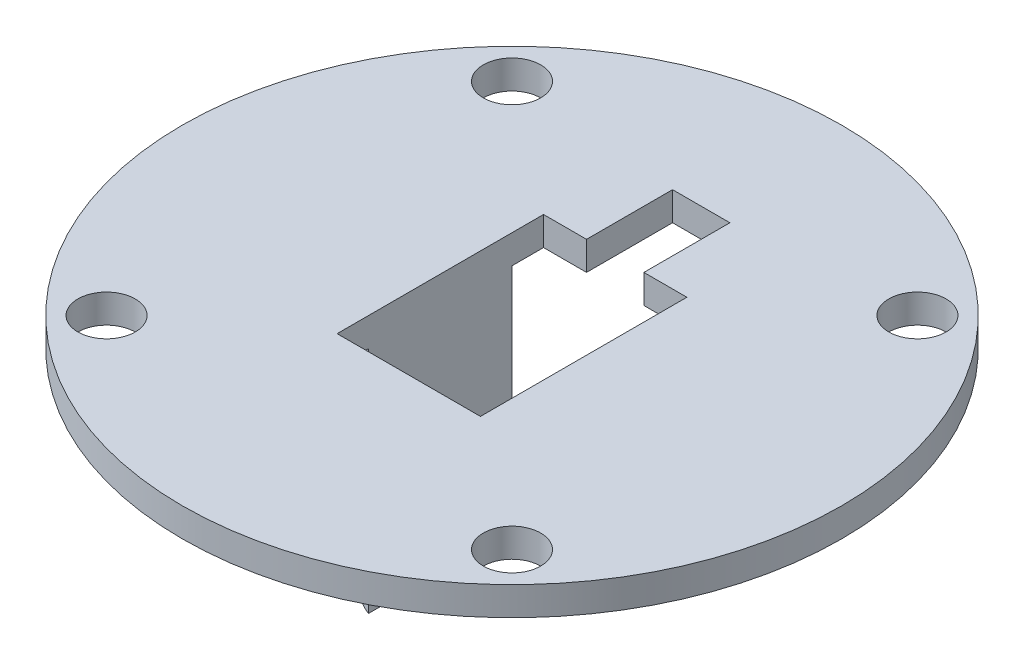
SolidWorks part; units mm, degrees
ref_plane "Front Plane" through (0, 0, 0) normal (0, 0, 1) x (1, 0, 0)
ref_plane "Top Plane" through (0, 0, 0) normal (0, 1, 0) x (1, 0, 0)
ref_plane "Right Plane" through (0, 0, 0) normal (1, 0, 0) x (0, 0, -1)
sketch "Sketch2" plane through (0, 0, 0) normal (0, 1, 0) x (1, 0, 0)
  circle A0 centre (0, 0) radius 57.5
  dimension "D1" = 115
extrude "Boss-Extrude1" add sketch "Sketch2" along normal blind 5
sketch "Sketch3" plane through (0, 5, 0) normal (0, 1, 0) x (1, 0, 0)
  line L0 (-35.3553, -35.3553) -> (35.3553, -35.3553) construction
  line L1 (35.3553, -35.3553) -> (35.3553, 35.3553) construction
  line L2 (35.3553, 35.3553) -> (-35.3553, 35.3553) construction
  line L3 (-35.3553, 35.3553) -> (-35.3553, -35.3553) construction
  circle A0 centre (-35.3553, 35.3553) radius 5
  circle A1 centre (35.3553, 35.3553) radius 5
  circle A2 centre (35.3553, -35.3553) radius 5
  circle A3 centre (-35.3553, -35.3553) radius 5
  dimension "D1" = 10
  dimension "D2" = 10
  dimension "D3" = 10
  dimension "D4" = 10
  dimension "D6" = 50
  dimension "D7" = 50
  dimension "D8" = 50
extrude "Cut-Extrude1" cut sketch "Sketch3" against normal through all
sketch "Sketch4" plane through (0, 5, 0) normal (0, 1, 0) x (1, 0, 0)
  line L1 (-12.5, -18) -> (12.5, -18)
  line L2 (-12.5, -18) -> (-12.5, 18)
  line L3 (-12.5, 18) -> (12.5, 18)
  line L4 (12.5, -18) -> (12.5, 18)
  line L5 (-12.5, -18) -> (12.5, 18) construction
  line L6 (-12.5, 18) -> (12.5, -18) construction
  point P0 (0, 0)
  dimension "D1" = 25
  dimension "D2" = 36
extrude "Cut-Extrude2" cut sketch "Sketch4" against normal through all
sketch "Sketch5" plane through (0, 0, 0) normal (0, -1, 0) x (1, 0, 0)
  line L0 (-12.5, 18) -> (12.5, 18) construction
  line L1 (-17.5, -12.5) -> (-12.5, -12.5)
  line L2 (-17.5, -12.5) -> (-17.5, 12.5)
  line L3 (-17.5, 12.5) -> (-12.5, 12.5)
  line L4 (-12.5, -12.5) -> (-12.5, 12.5)
  line L5 (-17.5, -12.5) -> (-12.5, 12.5) construction
  line L6 (-17.5, 12.5) -> (-12.5, -12.5) construction
  line L7 (-12.5, -18) -> (-12.5, 18) construction
  point P0 (-15, 0)
  dimension "D1" = 5
  dimension "D2" = 25
  dimension "D3" = 5.5
extrude "Boss-Extrude2" add sketch "Sketch5" along normal blind 40
fillet "Fillet1" radius 6 3 edges at (-17.5, -40, 0) (-17.5, -20, -12.5) (-17.5, -20, 12.5)
sketch "Sketch7" plane through (0, 5, 0) normal (0, 1, 0) x (1, 0, 0)
  line L0 (12.5, -18) -> (12.5, 18) construction
  line L1 (-5, 18) -> (5, 18)
  line L2 (-5, 18) -> (-5, 33)
  line L3 (-5, 33) -> (5, 33)
  line L4 (5, 18) -> (5, 33)
  line L5 (-5, 18) -> (5, 33) construction
  line L6 (-5, 33) -> (5, 18) construction
  line L7 (12.5, 18) -> (-12.5, 18) construction
  point P0 (0, 25.5)
  dimension "D1" = 15
  dimension "D2" = 10
  dimension "D3" = 7.5
extrude "Cut-Extrude3" cut sketch "Sketch7" against normal through all
